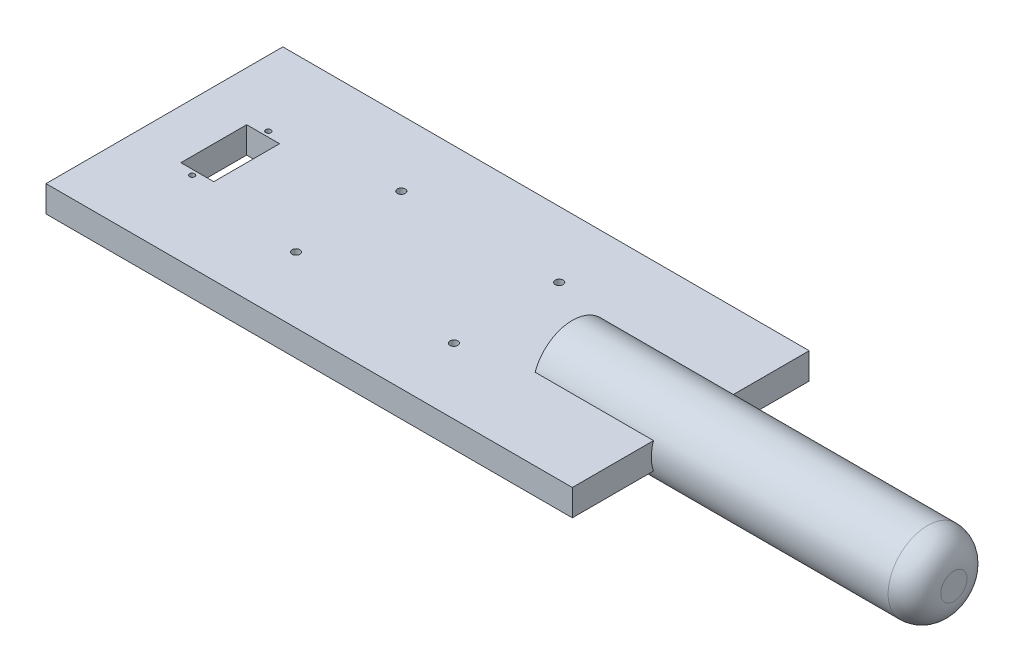
SolidWorks part; units mm, degrees
ref_plane "Alzado" through (0, 0, 0) normal (0, 0, 1) x (1, 0, 0)
ref_plane "Planta" through (0, 0, 0) normal (0, 1, 0) x (1, 0, 0)
ref_plane "Vista lateral" through (0, 0, 0) normal (1, 0, 0) x (0, 0, -1)
sketch "Croquis1" plane through (0, 0, 0) normal (0, 1, 0) x (1, 0, 0)
  line L0 (0, 0) -> (49310.8582, 0) construction
  line L1 (0, 0) -> (0, 49310.8582) construction
  line L3 (-100, -45) -> (100, -45)
  line L4 (-100, -45) -> (-100, 45)
  line L5 (-100, 45) -> (100, 45)
  line L6 (100, -45) -> (100, 45)
  line L7 (-100, -45) -> (100, 45) construction
  line L8 (-100, 45) -> (100, -45) construction
  line L9 (-81.25, -12.5) -> (-68.75, -12.5)
  line L10 (-81.25, -12.5) -> (-81.25, 12.5)
  line L11 (-81.25, 12.5) -> (-68.75, 12.5)
  line L12 (-68.75, -12.5) -> (-68.75, 12.5)
  line L13 (-81.25, -12.5) -> (-68.75, 12.5) construction
  line L14 (-81.25, 12.5) -> (-68.75, -12.5) construction
  circle A0 centre (-75, 14.5) radius 1
  circle A2 centre (-75, -14.5) radius 1
  point P5 (0, 0)
  point P10 (-75, 0)
  point P17 (0, 0)
  point P19 (0, 0)
  dimension "D5" = 2
  dimension "D1" = 90
  dimension "D2" = 200
  dimension "D3" = 25
  dimension "D4" = 12.5
  dimension "D6" = 2
  dimension "D7" = 75
extrude "Base" add sketch "Croquis1" along normal blind 10
sketch "Croquis2" plane through (0, 10, 0) normal (0, 1, 0) x (1, 0, 0)
  line L0 (0, 0) -> (50000, 0) construction
  line L1 (100, -45) -> (100, 45) construction
  line L2 (100, 45) -> (-100, 45) construction
  circle A0 centre (-30, 20) radius 1.5
  circle A3 centre (30, 20) radius 1.5
  circle A4 centre (30, -20) radius 1.5
  circle A5 centre (-30, -20) radius 1.5
  point P11 (0, 0)
  point P12 (0, 0)
  point P13 (0, 0)
  point P14 (0, 0)
  point P15 (0, 0)
  point P16 (26.0658, 20)
  point P17 (0, 0)
  point P18 (0, 0)
  point P19 (0, 0)
  point P20 (-15.9638, 20)
  point P21 (0, 0)
  dimension "D1" = 3
  dimension "D2" = 30
  dimension "D4" = 3
  dimension "D5" = 20
  dimension "D6" = 60
extrude "Cortar-Extruir1" cut sketch "Croquis2" against normal through all
sketch "Croquis3" plane through (100, 0, 0) normal (1, 0, 0) x (0, 0, -1)
  line L0 (-45, 10) -> (-45, 0) construction
  circle A0 centre (0, 5) radius 15
  point P2 (0, 0)
  point P6 (-45, 5)
  dimension "D1" = 30
extrude "Mango" add sketch "Croquis3" along normal blind 100 and the other way blind 45
fillet "Redondeo Mango" radius 10 1 edges at (200, 5, -15)
